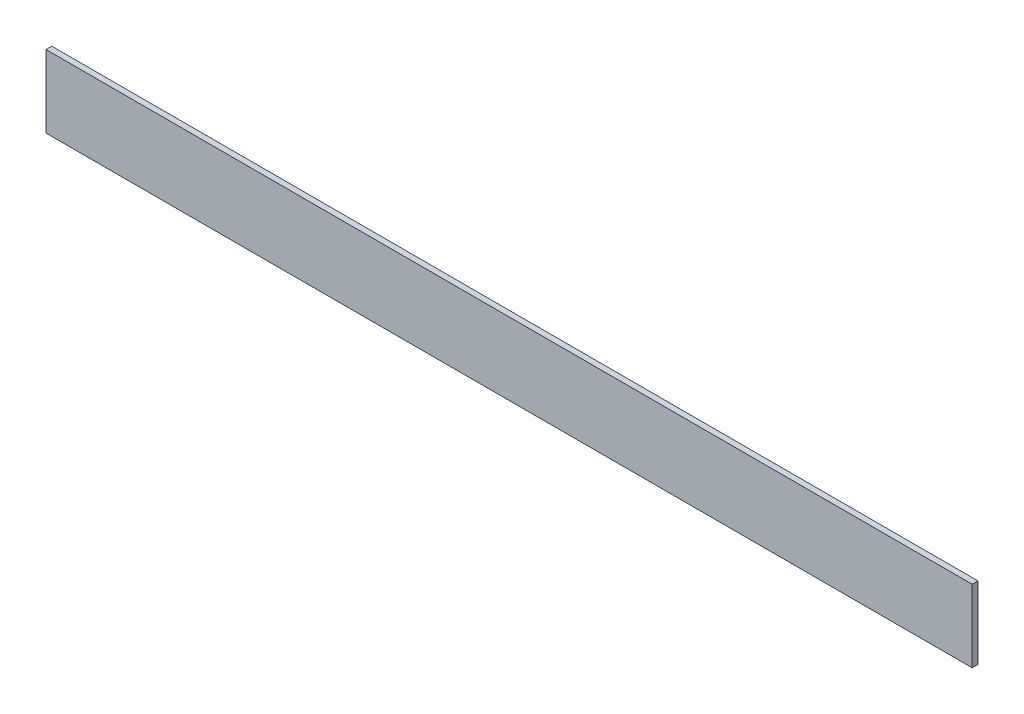
SolidWorks part; units mm, degrees
ref_plane "Спереди" through (0, 0, 0) normal (0, 0, 1) x (1, 0, 0)
ref_plane "Сверху" through (0, 0, 0) normal (0, 1, 0) x (1, 0, 0)
ref_plane "Справа" through (0, 0, 0) normal (1, 0, 0) x (0, 0, -1)
sketch "Эскиз1" plane through (0, 0, 0) normal (1, 0, 0) x (0, 0, -1)
  line L0 (0, 25) -> (0, 0)
  line L1 (0, 0) -> (25, 0)
extrude "Вытянуть-Тонкостенный1" add sketch "Эскиз1" along normal blind 320 thin thin type one direction reverse wall 2
sketch "Эскиз2" plane through (0, 0, 0) normal (0, -1, 0) x (1, 0, 0)
  line L0 (320, -25) -> (0, -25) construction
  line L1 (297, -25) -> (320, -25)
  line L2 (297, -25) -> (297, -2)
  line L3 (297, -2) -> (320, -2)
  line L4 (320, -25) -> (320, -2)
  line L5 (320, 0) -> (320, -25) construction
  dimension "D1" = 23
extrude "Вырез-Вытянуть1" cut sketch "Эскиз2" against normal through all
